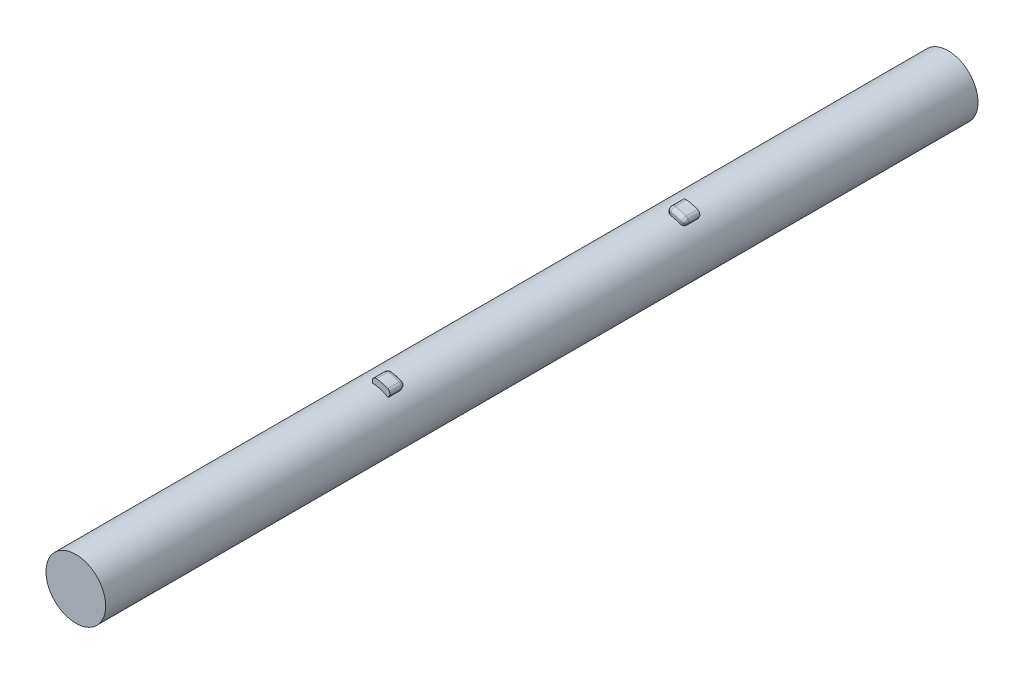
SolidWorks part; units mm, degrees
ref_plane "Płaszczyzna przednia" through (0, 0, 0) normal (0, 0, 1) x (1, 0, 0)
ref_plane "Płaszczyzna górna" through (0, 0, 0) normal (0, 1, 0) x (1, 0, 0)
ref_plane "Płaszczyzna prawa" through (0, 0, 0) normal (1, 0, 0) x (0, 0, -1)
sketch "Szkic1" plane through (0, 0, 0) normal (0, 0, 1) x (1, 0, 0)
  circle A0 centre (0, 0) radius 3.9
  dimension "D1" = 7.8
extrude "Dodanie-wyciągnięcie1" add sketch "Szkic1" along normal blind 114
ref_plane "Płaszczyzna2" through (0, 0, 106) normal (0, 0, 1) x (1, 0, 0)
sketch "Szkic4" plane through (0, 0, 0) normal (1, 0, 0) x (0, 0, -1)
  line L0 (-103, -0.2826) -> (-102, -0.2826) construction
  line L1 (-102, -0.2826) -> (-83, -0.2826) construction
  line L2 (-83, -0.2826) -> (-27, -0.2826) construction
  line L3 (-83, -0.2826) -> (-75.25, -0.2826)
  line L4 (-27, -0.2826) -> (-8, -0.2826) construction
  line L5 (-8, -0.2826) -> (0, -0.2826) construction
  line L6 (0, -3.9) -> (0, 3.9) construction
  line L7 (-75.25, -0.2826) -> (-34.75, -0.2826)
  line L8 (-34.75, -0.2826) -> (-27, -0.2826)
  line L10 (-75.25, -0.2826) -> (-73.25, -0.2826)
  line L11 (-75.25, -0.2826) -> (-75.25, 4.7174)
  line L12 (-75.25, 4.7174) -> (-73.25, 4.7174)
  line L13 (-73.25, -0.2826) -> (-73.25, 4.7174)
  line L14 (-34.75, -0.2826) -> (-36.75, -0.2826)
  line L15 (-34.75, -0.2826) -> (-34.75, 4.7174)
  line L16 (-34.75, 4.7174) -> (-36.75, 4.7174)
  line L17 (-36.75, -0.2826) -> (-36.75, 4.7174)
  dimension "D1" = 1
  dimension "D2" = 8
  dimension "D4" = 7.75
revolve "Obrót1" add sketch "Szkic4" angle 30 about L7
fillet "Zaokrąglenie5" radius 0.5 10 edges at (0, 4.7174, 74.25) (2.5, 4.0475, 74.25) (0, 4.3087, 73.25) (2.2855, 3.6761, 73.25) (1.2941, 4.547, 73.25) (0, 4.3087, 36.75) (2.2855, 3.6761, 36.75) (1.2941, 4.547, 36.75) (2.5, 4.0475, 35.75) (0, 4.7174, 35.75)
